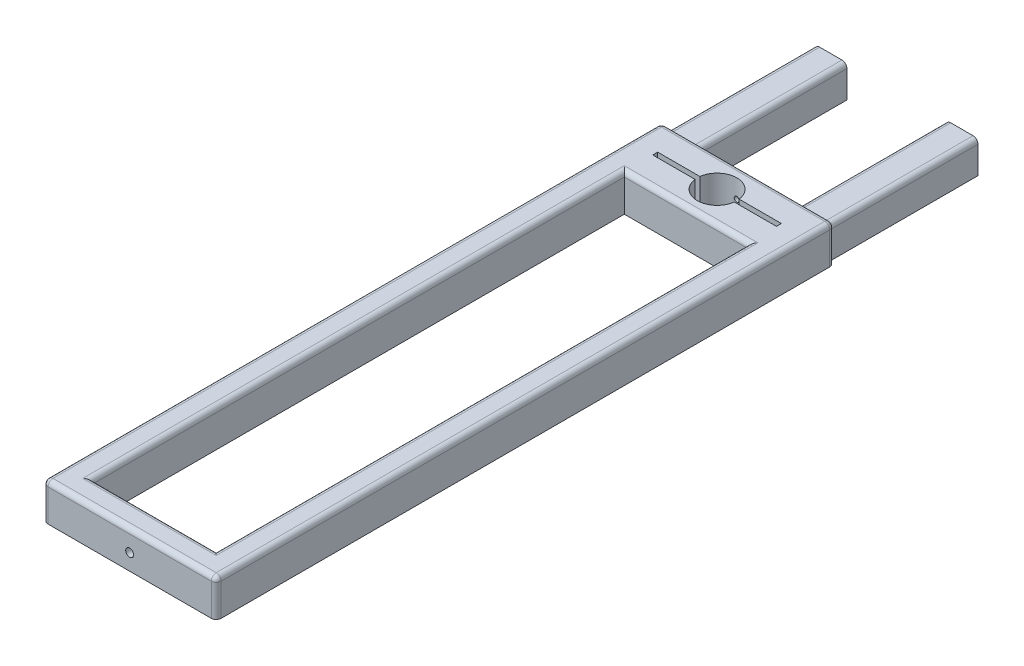
SolidWorks part; units mm, degrees
ref_plane "前视基准面" through (0, 0, 0) normal (0, 0, 1) x (1, 0, 0)
ref_plane "上视基准面" through (0, 0, 0) normal (0, 1, 0) x (1, 0, 0)
ref_plane "右视基准面" through (0, 0, 0) normal (1, 0, 0) x (0, 0, -1)
other "Configuration Table"
sketch "草图1" plane through (0, 0, 0) normal (0, 0, 1) x (1, 0, 0)
  line L1 (-35, -7.5) -> (35, -7.5)
  line L2 (-35, -7.5) -> (-35, 7.5)
  line L3 (-35, 7.5) -> (35, 7.5)
  line L4 (35, -7.5) -> (35, 7.5)
  line L5 (-35, -7.5) -> (35, 7.5) construction
  line L6 (-35, 7.5) -> (35, -7.5) construction
  point P0 (0, 0)
  dimension "D1" = 70
  dimension "D2" = 15
extrude "凸台-拉伸1" add sketch "草图1" along normal blind 250
sketch "草图2" plane through (0, 7.5, 0) normal (0, 1, 0) x (1, 0, 0)
  line L0 (35, -250) -> (-35, -250) construction
  line L5 (35, 0) -> (-35, 0) construction
  line L6 (-25, -25) -> (25, -25)
  line L7 (-35, -250) -> (-35, 0) construction
  line L8 (-25, -25) -> (-25, -240)
  line L9 (-25, -240) -> (25, -240)
  line L10 (25, -25) -> (25, -240)
  line L11 (35, -250) -> (35, 0) construction
  dimension "D1" = 25
  dimension "D2" = 10
  dimension "D3" = 10
  dimension "D4" = 10
extrude "切除-拉伸1" cut sketch "草图2" against normal blind 250
sketch "草图3" plane through (0, 7.5, 0) normal (0, 1, 0) x (1, 0, 0)
  line L0 (0, 0) -> (0, -25)
  line L1 (35, 0) -> (-35, 0) construction
  line L2 (25, -25) -> (-25, -25) construction
  line L4 (-25, -13.5) -> (25, -13.5)
  line L5 (-25, -13.5) -> (-25, -11.5)
  line L6 (-25, -11.5) -> (25, -11.5)
  line L7 (25, -13.5) -> (25, -11.5)
  line L8 (-25, -13.5) -> (25, -11.5) construction
  line L9 (-25, -11.5) -> (25, -13.5) construction
  circle A0 centre (0, -12.5) radius 8
  dimension "D1" = 16
  dimension "D2" = 50
  dimension "D3" = 2
extrude "切除-拉伸2" cut sketch "草图3" against normal blind 250 contours L6 A0 L0 | L0 A0 L6 | L4 A0 L0 | L0 A0 L4 | L4 A0 L6 L0 | L6 A0 L4 L0 | A0 L6 L5 L4 | A0 L4 L7 L6 | L6 L7 L4 L5 region at (3.2832, 7.5, 8.5582) region at (-3.2832, 7.5, 8.5582) region at (3.9896, 7.5, 12.5) region at (-3.9896, 7.5, 12.5) region at (16.4895, 7.5, 12.5) region at (-16.4895, 7.5, 12.5) region at (3.2832, 7.5, 16.4418) region at (-3.2832, 7.5, 16.4418)
fillet "圆角1" radius 2 1 edges at (-35, 7.5, 125) type face fillet first side face at (0, 7.5, 12.5) second side face at (-35, 0, 125)
fillet "圆角2" radius 2 1 edges at (1, 7.5, 0) type face fillet first side face at (-6.6828, 1.1828, 0) second side face at (0, 7.5, 12.5)
fillet "圆角3" radius 2 1 edges at (35, 7.5, 126) type face fillet first side face at (35, 1.1828, 100.3172) second side face at (0, 7.5, 12.5)
fillet "圆角4" radius 2 1 edges at (0, 7.5, 250) type face fillet first side face at (0, 1.9714, 250) second side face at (0, 7.5, 12.5)
fillet "圆角5" radius 2 4 edges at (0, 7.5, 240) (-25, 7.5, 132.5) (0, 7.5, 25) (25, 7.5, 132.5) type face fillet first side face at (0, 0, 25) first side face at (25, 0, 132.5) first side face at (0, 0, 240) first side face at (-25, 0, 132.5) second side face at (0, 7.5, 12.5)
sketch "草图4" plane through (0, 0, 250) normal (0, 0, 1) x (1, 0, 0)
  line L0 (0, 5.5) -> (0, -7.5)
  line L1 (33, 5.5) -> (-33, 5.5) construction
  line L2 (-33, -7.5) -> (33, -7.5) construction
  circle A0 centre (0, -1) radius 1.6
  dimension "D1" = 3.2
extrude "切除-拉伸3" cut sketch "草图4" against normal up to next contours A0
sketch "草图5" plane through (0, 0, 0) normal (0, 0, -1) x (-1, 0, 0)
  line L0 (33, -7.5) -> (-33, -7.5) construction
  line L1 (-33, 5.5) -> (-20, 5.5)
  line L2 (-33, 5.5) -> (-33, -7.5)
  line L3 (-33, -7.5) -> (-20, -7.5)
  line L4 (-20, 5.5) -> (-20, -7.5)
  line L6 (33, 5.5) -> (20, 5.5)
  line L7 (33, 5.5) -> (33, -7.5)
  line L8 (33, -7.5) -> (20, -7.5)
  line L9 (20, 5.5) -> (20, -7.5)
  dimension "D1" = 13
  dimension "D2" = 13
extrude "凸台-拉伸2" add sketch "草图5" along normal blind 60
fillet "圆角10" radius 2 1 edges at (33, 5.5, -30)
fillet "圆角11" radius 2 3 edges at (-33, 5.5, -30) (-20, 5.5, -30) (20, 5.5, -30)
sketch "草图6" plane through (0, 0, 0) normal (0, 0, -1) x (-1, 0, 0)
  circle A0 centre (0, 0) radius 1
  dimension "D1" = 2
extrude "切除-拉伸4" cut sketch "草图6" against normal up to next
